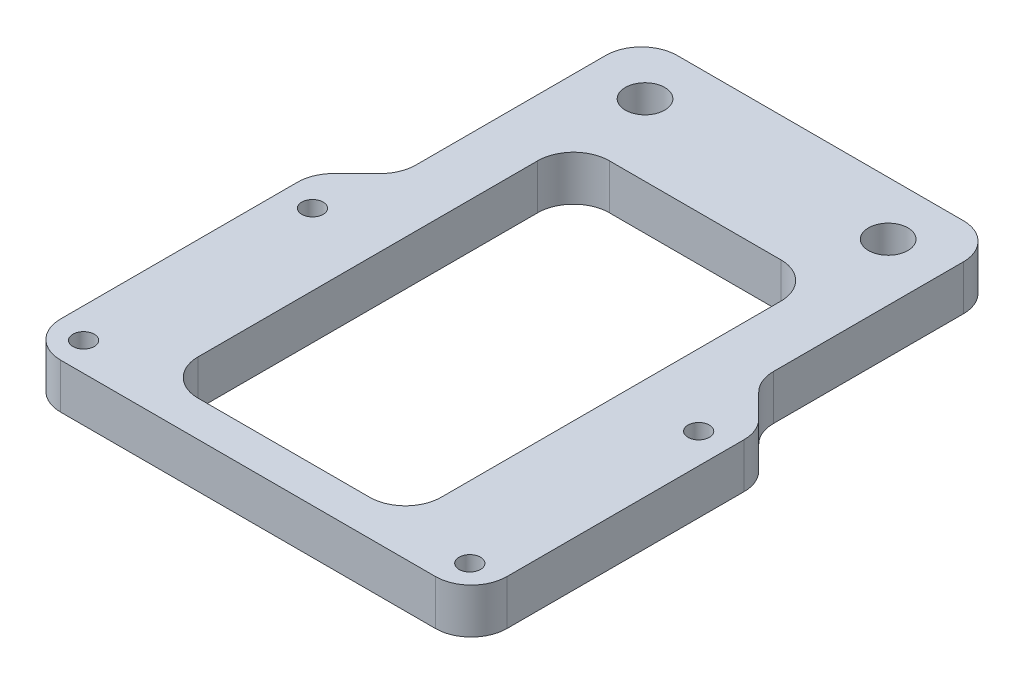
SolidWorks part; units mm, degrees
ref_plane "Front Plane" through (0, 0, 0) normal (0, 0, 1) x (1, 0, 0)
ref_plane "Top Plane" through (0, 0, 0) normal (0, 1, 0) x (1, 0, 0)
ref_plane "Right Plane" through (0, 0, 0) normal (1, 0, 0) x (0, 0, -1)
sketch "Sketch1" plane through (0, 0, 0) normal (0, 1, 0) x (1, 0, 0)
  line L1 (-19.812, -12.7) -> (19.812, -12.7)
  line L2 (-19.812, -12.7) -> (-19.812, 12.7)
  line L3 (-19.812, 12.7) -> (19.812, 12.7)
  line L4 (19.812, -12.7) -> (19.812, 12.7)
  line L5 (-19.812, -12.7) -> (19.812, 12.7) construction
  line L6 (-19.812, 12.7) -> (19.812, -12.7) construction
  line L7 (-17.145, -10.16) -> (17.145, -10.16) construction
  line L8 (-17.145, -10.16) -> (-17.145, 10.16) construction
  line L9 (-17.145, 10.16) -> (17.145, 10.16) construction
  line L10 (17.145, -10.16) -> (17.145, 10.16) construction
  line L11 (-17.145, -10.16) -> (17.145, 10.16) construction
  line L12 (-17.145, 10.16) -> (17.145, -10.16) construction
  line L17 (-13.97, -8.2785) -> (13.97, 8.2785) construction
  line L18 (-13.97, 8.2785) -> (13.97, -8.2785) construction
  circle A0 centre (-17.145, 10.16) radius 0.95
  circle A1 centre (-17.145, -10.16) radius 0.95
  circle A2 centre (17.145, -10.16) radius 0.95
  circle A3 centre (17.145, 10.16) radius 0.95
  point P0 (0, 0)
  point P6 (0, 0)
  point P15 (0, 0)
  dimension "D3" = 1.9
  dimension "D1" = 39.624
  dimension "D2" = 25.4
  dimension "D4" = 20.32
  dimension "D5" = 34.29
extrude "Boss-Extrude1" add sketch "Sketch1" along normal blind 4
sketch "Sketch3" plane through (0, 0, 0) normal (0, -1, 0) x (1, 0, 0)
  line L0 (0, 0) -> (0, 50000) construction
  line L1 (19.812, -12.7) -> (-19.812, -12.7) construction
  line L2 (15.875, -38.1) -> (-15.875, -38.1)
  line L3 (15.875, -38.1) -> (15.875, -12.7)
  line L4 (15.875, -12.7) -> (-15.875, -12.7)
  line L5 (-15.875, -38.1) -> (-15.875, -12.7)
  line L6 (15.875, -38.1) -> (-15.875, -12.7) construction
  line L7 (15.875, -12.7) -> (-15.875, -38.1) construction
  line L8 (10.795, -33.3375) -> (-10.795, -33.3375) construction
  circle A0 centre (-10.795, -33.3375) radius 1.75
  circle A1 centre (10.795, -33.3375) radius 1.75
  point P3 (0, -25.4)
  point P13 (0, -33.3375)
  dimension "D4" = 3.5
  dimension "D1" = 31.75
  dimension "D2" = 25.4
  dimension "D3" = 21.59
  dimension "D5" = 4.7625
extrude "Boss-Extrude2" add sketch "Sketch3" against normal up to surface (4 mm away) up to face at (0, 4, 0)
sketch "Sketch5" plane through (0, 0, 0) normal (0, -1, 0) x (1, 0, 0)
  line L0 (0, 0) -> (0, -50000) construction
  line L1 (-19.812, 12.7) -> (19.812, 12.7) construction
  line L2 (-10.795, -26.9875) -> (10.795, -26.9875)
  line L3 (-10.795, -26.9875) -> (-10.795, 9.525)
  line L4 (-10.795, 9.525) -> (10.795, 9.525)
  line L5 (10.795, -26.9875) -> (10.795, 9.525)
  line L6 (-10.795, -26.9875) -> (10.795, 9.525) construction
  line L7 (-10.795, 9.525) -> (10.795, -26.9875) construction
  circle A0 centre (-17.145, -10.16) radius 0.95 construction
  circle A1 centre (10.795, -33.3375) radius 1.75 construction
  point P3 (0, -8.7313)
  dimension "D1" = 6.35
  dimension "D2" = 6.35
  dimension "D3" = 3.175
extrude "Cut-Extrude2" cut sketch "Sketch5" against normal through all
chamfer "Chamfer1" distance 4.064 angle 45 2 edges at (15.875, 2, -12.7) (-15.875, 2, -12.7)
fillet "Fillet2" radius 3.175 12 edges at (-19.812, 2, 12.7) (19.812, 2, 12.7) (15.875, 2, -38.1) (-15.875, 2, -38.1) (-15.875, 2, -16.764) (-19.812, 2, -12.827) (19.812, 2, -12.827) (15.875, 2, -16.764) (10.795, 2, -26.9875) (10.795, 2, 9.525) (-10.795, 2, 9.525) (-10.795, 2, -26.9875)
